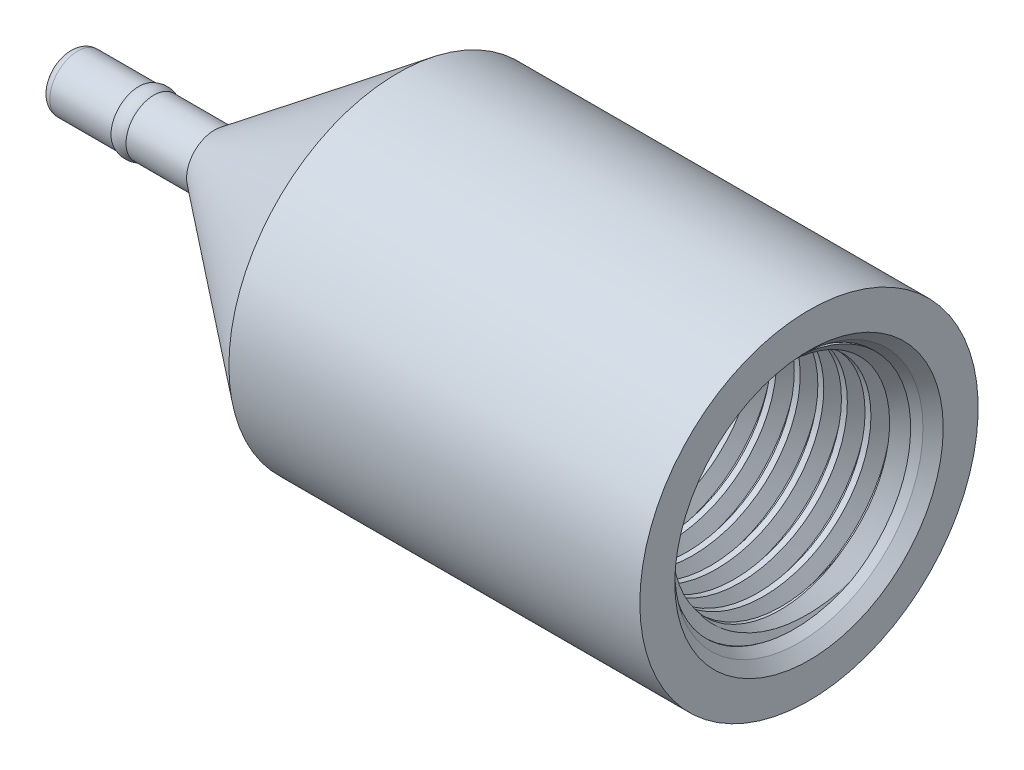
SolidWorks part; units mm, degrees
ref_plane "Front Plane" through (0, 0, 0) normal (0, 0, 1) x (1, 0, 0)
ref_plane "Top Plane" through (0, 0, 0) normal (0, 1, 0) x (1, 0, 0)
ref_plane "Right Plane" through (0, 0, 0) normal (1, 0, 0) x (0, 0, -1)
sketch "Sketch1" plane through (0, 0, 0) normal (0, 1, 0) x (1, 0, 0)
  line L0 (-15.7987, -12.8959) -> (3.8106, -12.8959) construction
  line L1 (-2.6078, -13.4135) -> (-8.7284, -13.4135)
  line L7 (-3.3586, -14.3959) -> (6.5267, -22.0037)
  line L8 (6.5267, -22.0037) -> (28.6485, -22.0037)
  line L9 (-2.6078, -13.4135) -> (6.5267, -18.6239)
  line L10 (6.5267, -18.6239) -> (7.6196, -19.2459)
  line L11 (7.6196, -19.2459) -> (27.6196, -19.2459)
  line L13 (28.6485, -19.9493) -> (28.6485, -22.0037)
  line L14 (27.6196, -19.2459) -> (28.6485, -19.9493)
  line L15 (-3.3586, -14.3959) -> (-6.6174, -14.3959)
  line L16 (-7.4276, -14.3959) -> (-9.5122, -14.3959)
  line L18 (-8.7284, -13.4135) -> (-11.22, -13.4135)
  line L20 (-9.5122, -14.3959) -> (-11.22, -14.3959)
  line L21 (-11.22, -13.4135) -> (-11.22, -14.3959)
  arc A0 (-6.6174, -14.3959) -> (-7.4276, -14.3959) centre (-7.0225, -13.6254) cw
  point P11 (-10.0685, -14.3123)
  point P16 (-8.4008, -14.3123)
  point P17 (-9.731, -14.3619)
  point P18 (-7.0225, -14.4959)
  point P19 (-9.5122, -14.3959)
  point P63 (28.6485, -19.9493)
  dimension "D5" = 1.6
  dimension "D1" = 6.35
  dimension "D2" = 1.5
  dimension "D3" = 20
revolve "Revolve1" add sketch "Sketch1" angle 360 about L0
fillet "Fillet1" radius 0.5 1 edges at (-11.22, 0, 14.3959)
thread "Thread1" pitch 1.27 method extrude profile "Thread Profile6" start angle 0, offset 1, length 20, pitch 1.27, diameter 12.7
ref_plane "Plane6" through (28.6196, 0, 19.2459) normal (0, -1, 0) x (0, 0, 1)
sketch "Thread Profile6" plane through (28.6196, 0, 19.2459) normal (0, -1, 0) x (0, 0, 1)
  line L0 (0, 0) -> (0, 1.27) construction
  line L11 (0, 0) -> (0, 1.1112)
  line L12 (0, 1.1112) -> (-0.6874, 0.7144)
  line L13 (-0.6874, 0.7144) -> (-0.6874, 0.3969)
  line L15 (-0.6874, 0.3969) -> (0, 0)
  line L17 (-0.6874, 0.5556) -> (0, 0.5556) construction
  point P2 (0, 0)
  dimension "Pitch" = 1.27
  dimension "Profile_Angle" = 60
  dimension "Profile_Land" = 0.3175
  dimension "Profile_Height" = 0.6874
sketch "Sketch8" plane through (28.6485, 0, 0) normal (1, 0, 0) x (0, 0, -1)
  circle A0 centre (-12.8959, 0) radius 7.2259
extrude "Cut-Extrude1" cut sketch "Sketch8" against normal blind 2 draft 45
